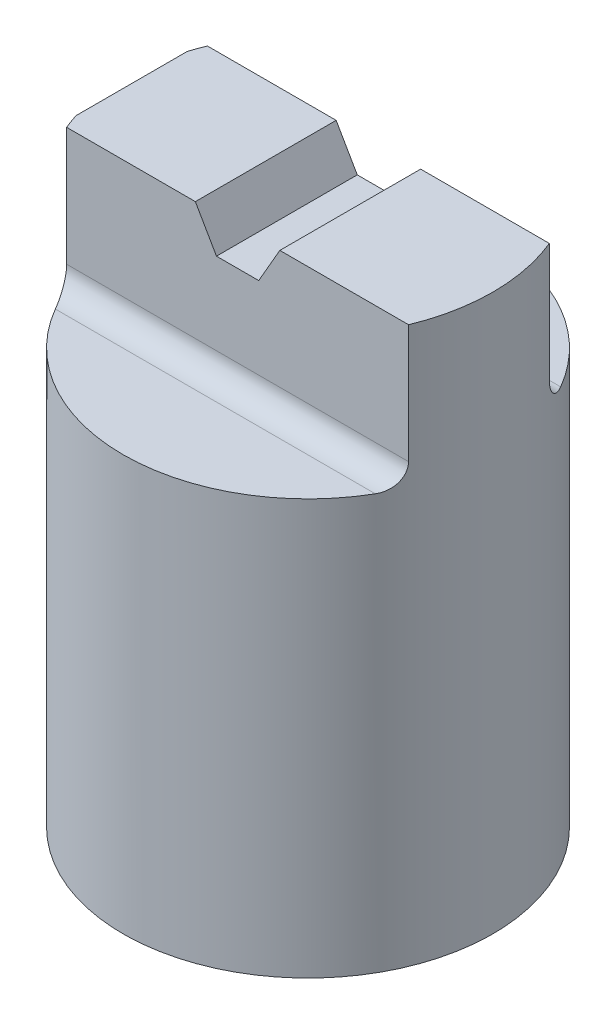
SolidWorks part; units mm, degrees
ref_plane "Alzado" through (0, 0, 0) normal (0, 0, 1) x (1, 0, 0)
ref_plane "Planta" through (0, 0, 0) normal (0, 1, 0) x (1, 0, 0)
ref_plane "Vista lateral" through (0, 0, 0) normal (1, 0, 0) x (0, 0, -1)
sketch "Croquis4" plane through (0, 0, 0) normal (0, 1, 0) x (1, 0, 0)
  circle A0 centre (0, 0) radius 12.6746
  dimension "D1" = 25.3492
extrude "Saliente-Extruir6" add sketch "Croquis4" along normal blind 38.1
sketch "Croquis7" plane through (0, 0, 0) normal (0, 0, 1) x (1, 0, 0)
  line L0 (-2.8956, 38.1) -> (-1.4478, 35.5854)
  line L1 (0, 35.5854) -> (0, 38.1) construction
  line L2 (0, 35.5854) -> (0, 0) construction
  line L7 (-1.4478, 35.5854) -> (1.4478, 35.5854)
  line L8 (-12.6746, 0) -> (12.6746, 0) construction
  line L9 (1.4478, 35.5854) -> (2.8956, 38.1)
  line L14 (-2.8956, 38.1) -> (2.8956, 38.1) construction
  line L15 (-2.8956, 38.1) -> (-1.4478, 35.5854) construction
  line L16 (-1.4478, 35.5854) -> (1.4478, 35.5854) construction
  line L17 (2.8956, 38.1) -> (-2.8956, 38.1)
  line L18 (1.4478, 35.5854) -> (2.8956, 38.1) construction
  line L19 (12.6746, 38.1) -> (-12.6746, 38.1) construction
  dimension "D1" = 5.7912
  dimension "D2" = 2.8956
  dimension "D3" = 2.5146
extrude "Cortar-Extruir2" cut sketch "Croquis7" against normal blind 38.1 and the other way blind 38.1 contours L17 L0 L7 L9
sketch "Croquis26" plane through (0, 0, 0) normal (0, 1, 0) x (1, 0, 0)
  line L0 (-12.6746, 0) -> (-12.0904, 0) construction
  line L2 (-12.0904, 0) -> (-12.0904, -3.8036)
  line L3 (-12.0904, 0) -> (-12.0904, 3.8036)
  circle A3 centre (0, 0) radius 12.6746 construction
  arc A4 (-12.0904, 3.8036) -> (-12.0904, -3.8036) centre (0, 0) ccw
  dimension "D1" = 0.5842
extrude "Cortar-Extruir8" cut sketch "Croquis26" along normal blind 48.26
sketch "Croquis32" plane through (0, 0, 0) normal (0, -1, 0) x (1, 0, 0)
  line L0 (0, -12.6746) -> (0, -12.0904) construction
  line L1 (0, -12.0904) -> (7.1928, -12.0904)
  line L2 (0, -12.0904) -> (-5.5943, -12.0904)
  arc A0 (-12.0904, -3.8036) -> (-12.0904, 3.8036) centre (0, 0) ccw construction
  arc A1 (-5.5943, -12.0904) -> (7.1928, -12.0904) centre (0.7992, 6.7412) ccw
  dimension "D1" = 0.5842
extrude "Cortar-Extruir10" cut sketch "Croquis32" against normal blind 55.88
sketch "Croquis34" plane through (0, 0, 0) normal (1, 0, 0) x (0, 0, -1)
  line L0 (0, 0) -> (0, 38.1) construction
  line L1 (12.0904, 38.1) -> (-12.3394, 38.1) construction
  line L2 (-4.826, 38.1) -> (4.826, 38.1) construction
  line L3 (-4.826, 38.1) -> (-4.826, 29.972)
  line L4 (-6.35, 28.448) -> (-12.6746, 28.448)
  line L5 (-12.6746, 35.5854) -> (-12.6746, 0) construction
  line L6 (-12.6746, 28.448) -> (-12.6746, 38.1)
  line L7 (-12.6746, 38.1) -> (-4.826, 38.1)
  line L8 (4.826, 38.1) -> (4.826, 29.972)
  line L9 (6.35, 28.448) -> (12.0904, 28.448)
  line L10 (12.0904, 0) -> (12.0904, 38.1) construction
  line L11 (12.0904, 28.448) -> (12.0904, 38.1)
  line L12 (12.0904, 38.1) -> (4.826, 38.1)
  line L13 (-4.826, 28.448) -> (4.826, 28.448) construction
  arc A0 (4.826, 29.972) -> (6.35, 28.448) centre (6.35, 29.972) ccw
  arc A1 (-4.826, 29.972) -> (-6.35, 28.448) centre (-6.35, 29.972) cw
  point P7 (0, 38.1)
  dimension "D3" = 1.524
  dimension "D1" = 9.652
  dimension "D2" = 9.652
extrude "Cortar-Extruir11" cut sketch "Croquis34" against normal blind 40.64 and the other way blind 38.1
sketch "Croquis35" plane through (-12.0904, 0, 0) normal (-1, 0, 0) x (0, 0, 1)
  line L0 (-2.3813, 26.7406) -> (-2.3813, 38.1) construction
  line L1 (-3.8036, 38.1) -> (3.8036, 38.1) construction
  text T0 "7/32"
  point P3 (-3.0439, 24.5505)
  point P4 (-1.6178, 38.1)
  point P7 (-0.9048, 28.3194)
  point P8 (-0.9557, 26.7406)
  point P9 (-2.0762, 38.1)
  point P10 (0, 38.1)
  dimension "D1" = 2.3813
extrude "Cortar-Extruir12" cut sketch "Croquis35" against normal blind 0.254
sketch "Croquis36" plane through (0, 0, 0) normal (0, -1, 0) x (1, 0, 0)
  line L0 (-6.0475, -11.1388) -> (-6.0475, 11.1388) construction
  arc A0 (3.8036, -12.0904) -> (-12.0904, 3.8036) centre (0, 0) ccw construction
  arc A1 (-12.0904, -3.8036) -> (-3.8036, -12.0904) centre (0, 0) ccw construction
  text T0 "UT2001-041" font "Century Gothic" height 2.3813
  point P3 (-5.5178, 11.4105)
  point P7 (-6.0475, -11.1388)
extrude "Cortar-Extruir13" cut sketch "Croquis36" against normal blind 0.254
